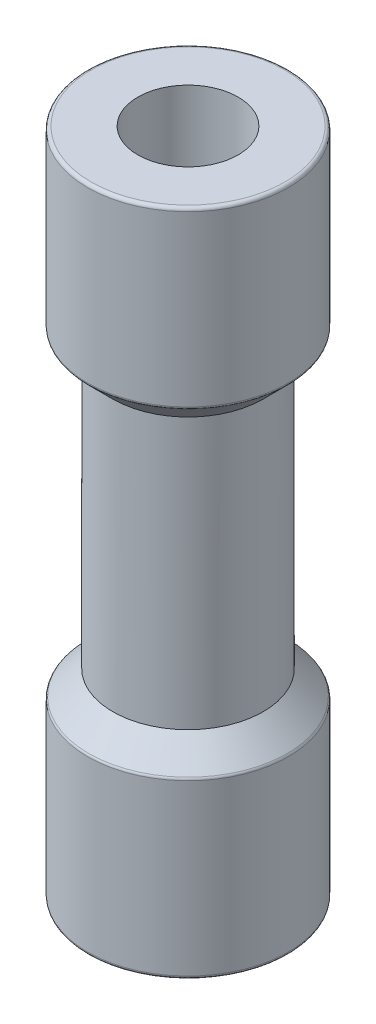
SolidWorks part; units mm, degrees
material "2.0966 (CuAl10Ni5Fe4)"
ref_plane "前视基准面" through (0, 0, 0) normal (0, 0, 1) x (1, 0, 0)
ref_plane "上视基准面" through (0, 0, 0) normal (0, 1, 0) x (1, 0, 0)
ref_plane "右视基准面" through (0, 0, 0) normal (1, 0, 0) x (0, 0, -1)
sketch "草图1" plane through (0, 0, 0) normal (0, 1, 0) x (1, 0, 0)
  circle A0 centre (0, 0) radius 3
  circle A1 centre (0, 0) radius 1.5
  dimension "D1" = 3
  dimension "D2" = 6
extrude "凸台-拉伸1" add sketch "草图1" along normal blind 6
sketch "草图2" plane through (0, 6, 0) normal (0, 1, 0) x (1, 0, 0)
  circle A0 centre (0, 0) radius 1.5 construction
  circle A1 centre (0, 0) radius 1.5
  circle A2 centre (0, 0) radius 2.25
  dimension "D1" = 4.5
extrude "凸台-拉伸2" add sketch "草图2" along normal blind 8
sketch "草图3" plane through (0, 14, 0) normal (0, 1, 0) x (1, 0, 0)
  circle A0 centre (0, 0) radius 1.5 construction
  circle A1 centre (0, 0) radius 1.5
  circle A2 centre (0, 0) radius 3 construction
  circle A3 centre (0, 0) radius 3
extrude "凸台-拉伸3" add sketch "草图3" along normal blind 6
chamfer "倒角1" distance 0.8 angle 45 2 edges at (0, 6, 3) (0, 14, 3)
fillet "圆角1" radius 0.1 4 edges at (0, 5.2, 3) (0, 14.8, 3) (0, 0, 3) (0, 20, 3)
